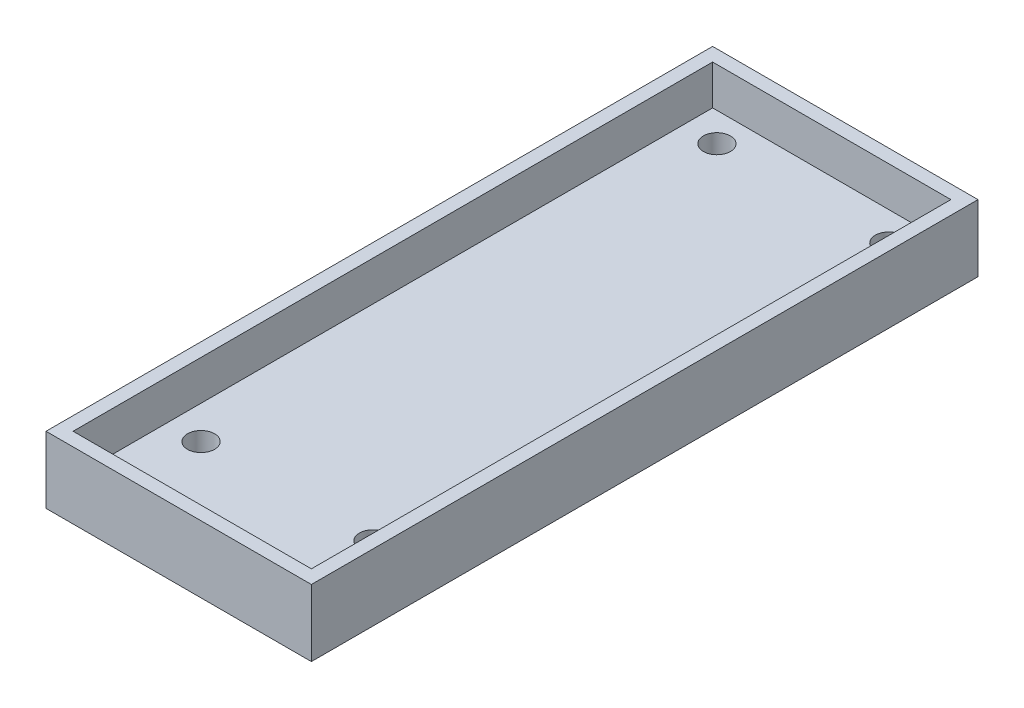
SolidWorks part; units mm, degrees
ref_plane "Front Plane" through (0, 0, 0) normal (0, 0, 1) x (1, 0, 0)
ref_plane "Top Plane" through (0, 0, 0) normal (0, 1, 0) x (1, 0, 0)
ref_plane "Right Plane" through (0, 0, 0) normal (1, 0, 0) x (0, 0, -1)
sketch "Sketch1" plane through (0, 0, 0) normal (0, 1, 0) x (1, 0, 0)
  line L0 (14.7, -36.925) -> (14.7, 36.925)
  line L1 (12.7, -34.925) -> (-12.7, -34.925)
  line L2 (12.7, -34.925) -> (12.7, 34.925)
  line L3 (12.7, 34.925) -> (-12.7, 34.925)
  line L4 (-12.7, -34.925) -> (-12.7, 34.925)
  line L5 (12.7, -34.925) -> (-12.7, 34.925) construction
  line L6 (12.7, 34.925) -> (-12.7, -34.925) construction
  line L7 (14.7, 36.925) -> (-14.7, 36.925)
  line L8 (-14.7, -36.925) -> (-14.7, 36.925)
  line L9 (14.7, -36.925) -> (-14.7, -36.925)
  line L10 (13.2, -35.425) -> (13.2, 35.425)
  line L11 (13.2, 35.425) -> (-13.2, 35.425)
  line L12 (-13.2, -35.425) -> (-13.2, 35.425)
  line L13 (13.2, -35.425) -> (-13.2, -35.425)
  point P0 (0, 0)
  dimension "D1" = 25.4
  dimension "D2" = 69.85
  dimension "D3" = 2
  dimension "D4" = 0.5
extrude "Boss-Extrude1" add sketch "Sketch1" against normal blind 3 contours L4 L1 L2 L3 | L13 L10 L11 L12 L1 L4 L3 L2 | L9 L0 L7 L8 L10 L13 L12 L11 region at (0, 0, 36.1301) region at (0, 0, 0) region at (0, 0, 35.3494)
extrude "Boss-Extrude2" add sketch "Sketch1<3>" along normal blind 4.4 contours L9 L0 L7 L8 L10 L13 L12 L11 region at (0, 0, 36.1301)
sketch "Sketch1<3>" plane through (0, 0, 0) normal (0, 1, 0) x (1, 0, 0) same geometry as "Sketch1"
sketch "Sketch2" plane through (0, 0, 0) normal (0, 1, 0) x (1, 0, 0)
  line L0 (-12.7, -34.925) -> (-12.7, 34.925) construction
  line L1 (-9.525, 32.225) -> (9.525, 32.225)
  line L2 (-9.525, 32.225) -> (-9.525, -24.925)
  line L3 (-9.525, -24.925) -> (9.525, -24.925)
  line L4 (9.525, 32.225) -> (9.525, -24.925)
  line L5 (12.7, -34.925) -> (12.7, 34.925) construction
  line L6 (12.7, 34.925) -> (-12.7, 34.925) construction
  circle A0 centre (-9.525, 32.225) radius 1.5
  circle A1 centre (9.525, 32.225) radius 1.5
  circle A2 centre (9.525, -24.925) radius 1.5
  circle A3 centre (-9.525, -24.925) radius 1.5
  dimension "D5" = 3
  dimension "D1" = 3.175
  dimension "D2" = 3.175
  dimension "D3" = 2.7
  dimension "D4" = 57.15
extrude "Cut-Extrude1" cut sketch "Sketch2" against normal through all both and the other way through all contours L4 A1 L1 | L1 A1 L4 | A0 | A3 | A2 region at (9.7372, 0, -32.4372) region at (8.8884, 0, -31.5884)
